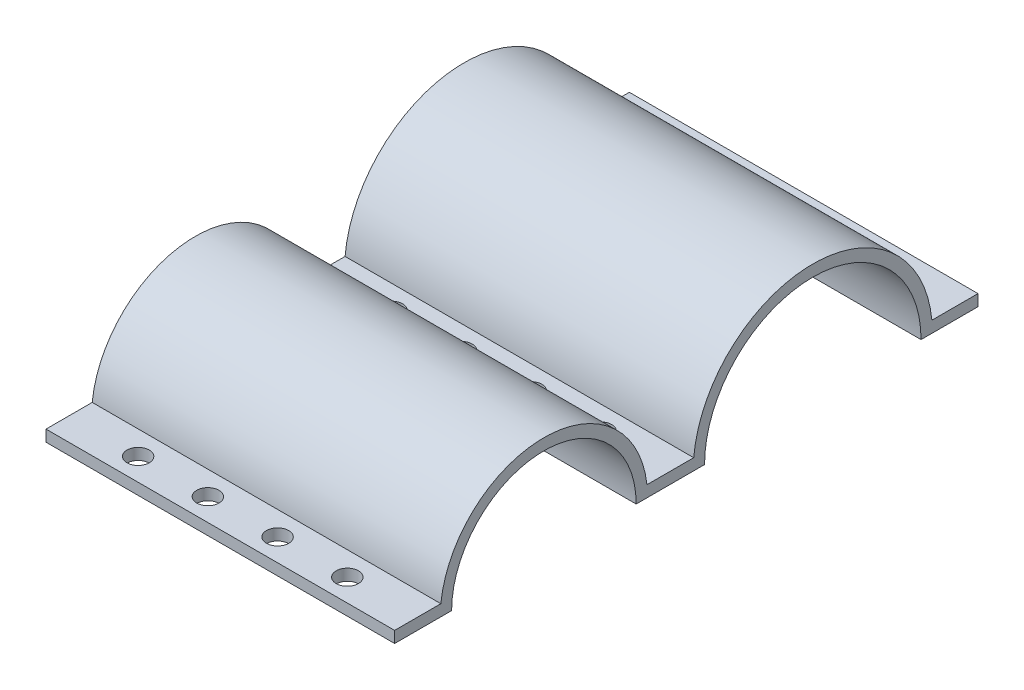
SolidWorks part; units mm, degrees
ref_plane "Front Plane" through (0, 0, 0) normal (0, 0, 1) x (1, 0, 0)
ref_plane "Top Plane" through (0, 0, 0) normal (0, 1, 0) x (1, 0, 0)
ref_plane "Right Plane" through (0, 0, 0) normal (1, 0, 0) x (0, 0, -1)
sketch "Sketch2" plane through (0, 0, 0) normal (1, 0, 0) x (0, 0, -1)
  line L0 (0, 0) -> (-10, 0)
  line L1 (-102.4, 0) -> (-102.4, 2)
  line L3 (0, 2) -> (0, 0)
  line L4 (-48, 0) -> (-60, 0)
  line L5 (-92.4, 0) -> (-102.4, 0)
  line L6 (0, 2) -> (-8.0955, 2)
  line L7 (-49.9045, 2) -> (-58.1102, 2)
  line L8 (-94.2898, 2) -> (-102.4, 2)
  line L9 (-102.4, 0) -> (-92.4, 0) construction
  line L10 (-102.4, 0) -> (-92.4, 0) construction
  arc A0 (-60, 0) -> (-92.4, 0) centre (-76.2, 0) ccw
  arc A1 (-10, 0) -> (-48, 0) centre (-29, 0) ccw
  arc A2 (-8.0955, 2) -> (-49.9045, 2) centre (-29, 0) ccw
  arc A3 (-58.1102, 2) -> (-94.2898, 2) centre (-76.2, 0) ccw
  point P4 (-76.2, 16.2)
  dimension "D2" = 16.2
  dimension "D4" = 19
  dimension "D3" = 10
  dimension "D6" = 2
extrude "Boss-Extrude1" add sketch "Sketch2" along normal blind 61.2
sketch "Sketch3" plane through (0, 2, 0) normal (0, 1, 0) x (1, 0, 0)
  line L0 (61.2, 0) -> (61.2, -8.0955) construction
  line L1 (61.2, -102.4) -> (0, -102.4) construction
  line L2 (61.2, 0) -> (0, 0) construction
  line L3 (0, 0) -> (0, -8.0955) construction
  line L4 (61.2, 0) -> (61.2, -8.0955) construction
  line L5 (0, 0) -> (0, -8.0955) construction
  line L6 (61.2, -49.9045) -> (61.2, -58.1102) construction
  line L7 (0, -60) -> (0, -48) construction
  line L8 (61.2, 0) -> (0, 0) construction
  line L9 (61.2, -49.9045) -> (61.2, -58.1102) construction
  line L10 (0, -60) -> (0, -48) construction
  line L11 (61.2, -49.9045) -> (0, -49.9045) construction
  circle A0 centre (12.24, -3.93) radius 1.95
  circle A1 centre (24.48, -3.93) radius 1.95
  circle A2 centre (36.72, -3.93) radius 1.95
  circle A3 centre (48.96, -3.93) radius 1.95
  circle A4 centre (12.24, -54.0074) radius 1.95
  circle A5 centre (24.48, -54.0074) radius 1.95
  circle A6 centre (36.72, -54.0074) radius 1.95
  circle A7 centre (48.96, -54.0074) radius 1.95
  circle A8 centre (12.24, -98.47) radius 1.95
  circle A9 centre (24.48, -98.47) radius 1.95
  circle A10 centre (36.72, -98.47) radius 1.95
  circle A11 centre (48.96, -98.47) radius 1.95
  point P26 (0, 0)
  point P27 (0, 0)
  point P28 (0, 0)
  point P29 (0, 0)
  point P30 (0, 0)
  point P36 (61.2, -4.0477)
  point P39 (0, -3.93)
  point P43 (61.2, -4.0477)
  point P46 (0, 0)
  point P47 (0, 0)
  point P48 (0, 0)
  dimension "D1" = 3.9
  dimension "D4" = 12.24
  dimension "D5" = 12.24
  dimension "D6" = 12.24
  dimension "D2" = 3.93
  dimension "D3" = 12.24
  dimension "D7" = 61.2
  dimension "D8" = 3.93
  dimension "D9" = 8.2057
  dimension "D10" = 4.1028
extrude "Cut-Extrude1" cut sketch "Sketch3" against normal up to surface (2 mm away) up to face at (30.6, 0, 97.4)
equation "\"MotorDIA\"= 37' Motor Diameter"
equation "\"SyringeDIA\"= 31.4'60ml Syringe Diameter"
equation "\"MotorShaftDIA\"= 6'Motor Shaft Dia"
equation "\"MotorKeyway\"= 1'Motor Shaft Keyway Depth"
equation "\"MotorLength\"= 56.7'Motor Length Excluding Shaft"
equation "\"SyringeLength\"= 117.3'60ml Syringe Length Excluding Nozzle"
equation "\"3Dtol\"= .5'Sizing Tolerance for 3D printed parts"
equation "\"ChamberDIA\"= 100 - 4'Buoyancy Chamber inner Diameter"
equation "\"ChamberThk\"= 2mm'Buoyancy Chamber Wall Thickness"
equation "\"BearingOD\"= 10"
equation "\"BearingID\"= 4"
equation "\"Bearingwidth\"= 4"
equation "\"ShaftDIA\"= 4"
equation "\"D1@Boss-Extrude1\"=\"MotorLength\"+\"3Dtol\"+4"
equation "\"D4@Sketch3\"=\"D3@Sketch3\""
equation "\"D5@Sketch3\"=\"D3@Sketch3\""
equation "\"D6@Sketch3\"=\"D3@Sketch3\""
equation "\"D2@Sketch2\"=\"SyringeDIA\"/2+\"3Dtol\""
equation "\"D4@Sketch2\"=\"MotorDIA\"/2 + \"3Dtol\""
equation "\"D3@Sketch3\"=\"D7@Sketch3\"/5"
equation "\"D10@Sketch3\"=\"D9@Sketch3\"/2"
